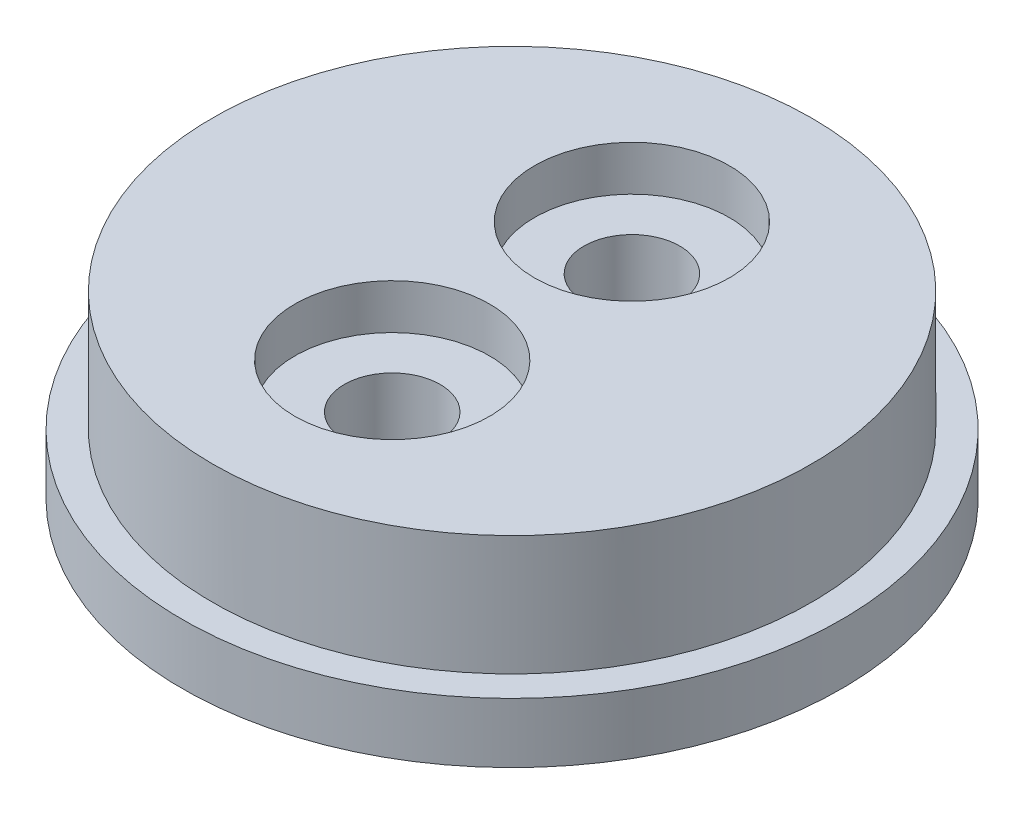
SolidWorks part; units mm, degrees
ref_plane "Front Plane" through (0, 0, 0) normal (0, 0, 1) x (1, 0, 0)
ref_plane "Top Plane" through (0, 0, 0) normal (0, 1, 0) x (1, 0, 0)
ref_plane "Right Plane" through (0, 0, 0) normal (1, 0, 0) x (0, 0, -1)
sketch "Sketch1" plane through (0, 0, 0) normal (0, 1, 0) x (1, 0, 0)
  circle A0 centre (0, 0) radius 10
  dimension "D1" = 20
extrude "Boss-Extrude1" add sketch "Sketch1" along normal blind 6
sketch "Sketch2" plane through (0, 6, 0) normal (0, 1, 0) x (1, 0, 0)
  line L0 (0, 7.9744) -> (0, -8.0985) construction
  circle A2 centre (0, 0) radius 4 construction
  circle A3 centre (0, 4) radius 3.25
  circle A4 centre (0, -4) radius 3.25
  point P12 (0, 0)
  dimension "D1" = 8
  dimension "D2" = 6.5
  dimension "D3" = 2
extrude "Cut-Extrude1" cut sketch "Sketch2" against normal blind 1.5
sketch "Sketch4" plane through (0, 0, 0) normal (0, -1, 0) x (1, 0, 0)
  circle A0 centre (0, 0) radius 11
  dimension "D1" = 22
extrude "Boss-Extrude2" add sketch "Sketch4" against normal blind 2
sketch "Sketch3" plane through (0, 6, 0) normal (0, 1, 0) x (1, 0, 0)
  line L0 (0, 8.0571) -> (0, -8.4294) construction
  circle A0 centre (0, 4) radius 1.6
  circle A1 centre (0, -4) radius 1.6
  circle A2 centre (0, 0) radius 4 construction
  dimension "D1" = 8
  dimension "D2" = 3.2
extrude "Cut-Extrude2" cut sketch "Sketch3" against normal through all
